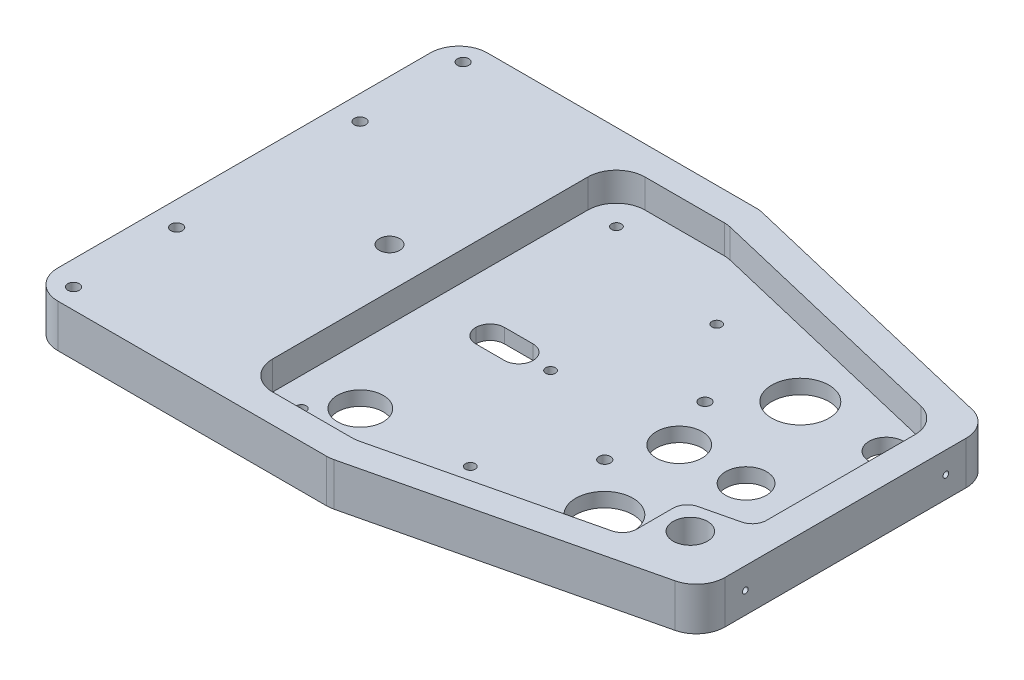
SolidWorks part; units mm, degrees
material "Carvalho"
ref_plane "Plano frontal" through (0, 0, 0) normal (0, 0, 1) x (1, 0, 0)
ref_plane "Plano superior" through (0, 0, 0) normal (0, 1, 0) x (1, 0, 0)
ref_plane "Plano direito" through (0, 0, 0) normal (1, 0, 0) x (0, 0, -1)
sketch "Esboço1" plane through (0, 0, 0) normal (0, 1, 0) x (1, 0, 0)
  line L0 (210, 50) -> (105, 75)
  line L1 (0, -75) -> (105, -75)
  line L2 (0, -75) -> (0, 75)
  line L3 (0, 75) -> (105, 75)
  line L4 (210, -50) -> (210, 50)
  line L7 (105, -75) -> (210, -50)
  line L8 (-14.8259, 0) -> (14.392, 0) construction
  line L9 (0, 21.2472) -> (0, -16.7598) construction
  circle A0 centre (50.8, 0) radius 3.5719
  circle A1 centre (175.26, 0) radius 7.14
  circle A2 centre (151.92, 0) radius 8
  circle A3 centre (151.92, 0) radius 8 construction
  circle A4 centre (8.5, -68) radius 2
  circle A5 centre (8.5, -32) radius 2
  circle A6 centre (8.5, -68) radius 2 construction
  circle A7 centre (8.5, -32) radius 2 construction
  circle A8 centre (8.5, 32) radius 2
  circle A9 centre (8.5, 68) radius 2
  point P0 (0, 0)
  dimension "D3" = 7.1437
  dimension "D5" = 14.28
  dimension "D1" = 25
  dimension "D2" = 150
  dimension "D4" = 50.8
  dimension "D6" = 210
  dimension "D7" = 175.26
  dimension "D8" = 105
extrude "Ressalto-extrusão1" add sketch "Esboço1" along normal blind 15
sketch "Esboço2" plane through (210, 0, 0) normal (1, 0, 0) x (0, 0, -1)
  line L0 (0, 15) -> (0, 0) construction
  line L1 (-50, 15) -> (50, 15) construction
  circle A0 centre (35, 7.5) radius 1
  circle A1 centre (-35, 7.5) radius 1
  point P9 (0, 7.5)
  dimension "D1" = 2
  dimension "D2" = 35
extrude "Corte-extrusão1" cut sketch "Esboço2" against normal blind 10
sketch "Esboço3" plane through (0, 15, 0) normal (0, 1, 0) x (1, 0, 0)
  line L0 (200, 42.1014) -> (200, -42.1014)
  line L2 (65, -65) -> (65, 65)
  line L6 (210, -50) -> (210, 50) construction
  line L7 (0, 75) -> (0, -75) construction
  line L8 (-22.821, 0) -> (224.4652, 0) construction
  line L9 (65, 65) -> (103.8259, 65)
  line L10 (103.8259, 65) -> (200, 42.1014)
  line L11 (65, -65) -> (103.8259, -65)
  line L12 (103.8259, -65) -> (200, -42.1014)
  line L13 (105, -75) -> (210, -50) construction
  line L14 (0, -75) -> (105, -75) construction
  line L15 (180, -26.3042) -> (200, -21.5423)
  line L16 (180, -46.8633) -> (180, -26.3042)
  circle M12 centre (151.92, 0) radius 8
  circle M14 centre (175.26, 0) radius 7.14
  dimension "D1" = 10
  dimension "D2" = 65
  dimension "D3" = 10
  dimension "D4" = 10
  dimension "D5" = 20
  dimension "D6" = 20
extrude "Corte-extrusão2" cut sketch "Esboço3" against normal blind 10 contours L2 L8 L0 L10 L9 M12 M14 | L8 L2 L11 L12 L16 L15 L0 M14 M12 region at (122.8919, 15, 29.2811) region at (126.5743, 15, -29.5512)
fillet "Filete1" radius 10 11 edges at (105, 7.5, 75) (0, 7.5, 75) (0, 7.5, -75) (210, 7.5, 50) (105, 7.5, -75) (210, 7.5, -50) (200, 10, -42.1014) (103.8259, 10, 65) (65, 10, 65) (103.8259, 10, -65) (65, 10, -65)
sketch "Esboço5" plane through (0, 0, 0) normal (0, -1, 0) x (1, 0, 0)
  line L0 (175.26, 0) -> (90.92, 0) construction
  line L2 (143.42, 17.5) -> (143.42, -17.5) construction
  line L3 (175.26, 0) -> (101.1849, 0) construction
  line L8 (80.92, -5) -> (100.92, -5)
  line L9 (80.92, -5) -> (80.92, 5)
  line L10 (80.92, 5) -> (100.92, 5)
  line L11 (100.92, -5) -> (100.92, 5)
  line L12 (80.92, -5) -> (100.92, 5) construction
  line L13 (80.92, 5) -> (100.92, -5) construction
  circle A0 centre (143.42, 17.5) radius 2
  circle A1 centre (143.42, -17.5) radius 2
  point P5 (143.42, 0)
  dimension "D6" = 4
  dimension "D1" = 35
  dimension "D2" = 42.5
  dimension "D3" = 20
  dimension "D4" = 31.84
  dimension "D5" = 10
extrude "Corte-extrusão4" cut sketch "Esboço5" against normal through all
fillet "Filete2" radius 5 4 edges at (80.92, 2.5, -5) (80.92, 2.5, 5) (100.92, 2.5, 5) (100.92, 2.5, -5)
fillet "Filete3" radius 5 3 edges at (180, 10, 46.8633) (180, 10, 26.3042) (200, 10, 21.5423)
sketch "Esboço6" plane through (0, 15, 0) normal (0, 1, 0) x (1, 0, 0)
  line L0 (224.3981, 0) -> (150.0179, 0) construction
  circle A0 centre (190, -34.2028) radius 6
  circle A1 centre (190, 34.2028) radius 6
  circle A2 centre (160, 34.2028) radius 10
  arc A3 (200, 34.2028) -> (192.3162, 43.9309) centre (190, 34.2028) ccw construction
  circle A4 centre (160, -34.2028) radius 10
  dimension "D1" = 12
  dimension "D2" = 20
  dimension "D3" = 30
extrude "Corte-extrusão5" cut sketch "Esboço6" against normal through all
sketch "Esboço7" plane through (0, 0, 0) normal (0, -1, 0) x (1, 0, 0)
  circle A0 centre (85.3, 44.7) radius 8
  circle A2 centre (85.3, 44.7) radius 7 construction
  circle A3 centre (75, 55) radius 1.7
  circle A4 centre (75, 55) radius 1.7 construction
  circle A5 centre (122, 43) radius 1.7
  circle A6 centre (107, 0) radius 1.7
  circle A7 centre (75, -55) radius 1.7
  circle A8 centre (122, -43) radius 1.7
  dimension "D1" = 1
extrude "Corte-extrusão6" cut sketch "Esboço7" against normal through all contours A3 | A6 | A5 | A7 | A8 | A0
